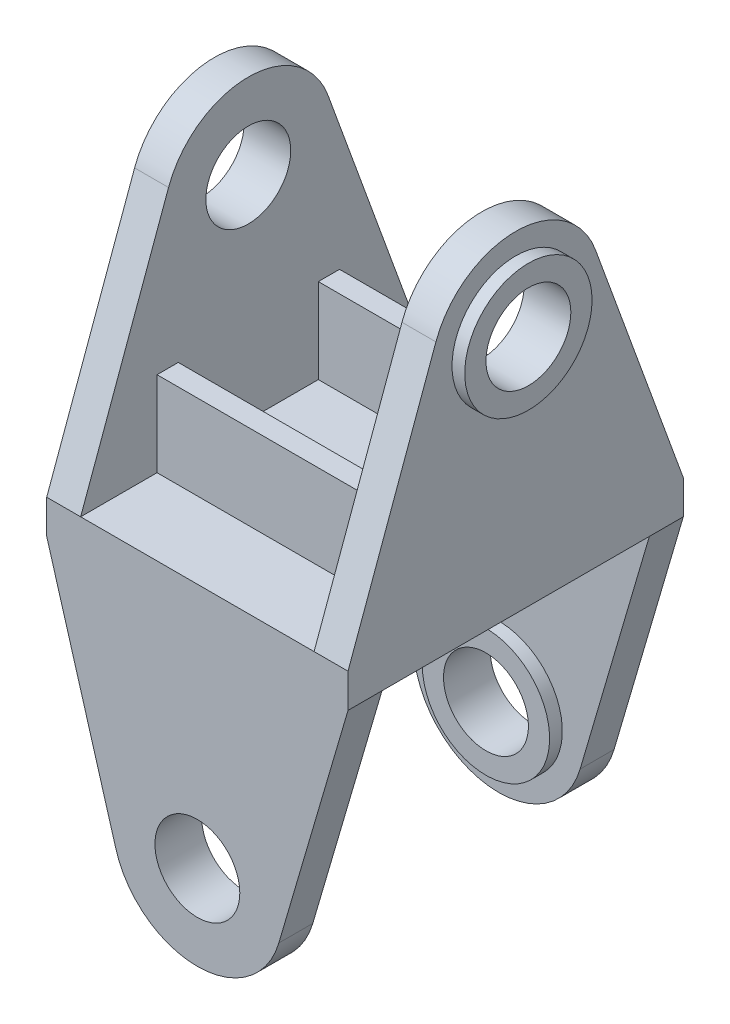
SolidWorks part; units mm, degrees
ref_plane "Front Plane" through (0, 0, 0) normal (0, 0, 1) x (1, 0, 0)
ref_plane "Top Plane" through (0, 0, 0) normal (0, 1, 0) x (1, 0, 0)
ref_plane "Right Plane" through (0, 0, 0) normal (1, 0, 0) x (0, 0, -1)
sketch "Sketch1" plane through (0, 0, 0) normal (1, 0, 0) x (0, 0, -1)
  line L0 (0, 0) -> (-17333.0338, 0) construction
  line L1 (0, 0) -> (0, -17333.0338) construction
  line L2 (39.5, -50) -> (18.7919, 6.8456)
  line L3 (-39.5, -50) -> (39.5, -50)
  line L4 (-39.5, -50) -> (-39.5, -58)
  line L5 (-39.5, -58) -> (39.5, -58)
  line L6 (39.5, -50) -> (39.5, -58)
  line L7 (0, -58) -> (0, -50) construction
  line L8 (-39.5, -54) -> (39.5, -54) construction
  line L9 (-39.5, -50) -> (-18.7919, 6.8456)
  circle A0 centre (0, 0) radius 10
  arc A1 (18.7919, 6.8456) -> (-18.7919, 6.8456) centre (0, 0) ccw
  circle A2 centre (0, 0) radius 15
  point P9 (0, -54)
  dimension "D1" = 20
  dimension "D2" = 30
  dimension "D3" = 40
  dimension "D4" = 79
  dimension "D5" = 8
  dimension "D6" = 50
extrude "Boss-Extrude1" add sketch "Sketch1" against normal blind 8 contours L2 A1 L9 L3 A2 | L6 L3 L4 L5 region at (0, -26.3684, 0) region at (0, -54, 0)
extrude "Boss-Extrude2" add sketch "Sketch1<3>" against normal blind 8 and the other way blind 3 contours A2 A0 region at (0, 0, 14.5757)
sketch "Sketch1<3>" plane through (0, 0, 0) normal (1, 0, 0) x (0, 0, -1) same geometry as "Sketch1"
extrude "Boss-Extrude3" add sketch "Sketch1<4>" against normal blind 8 from offset 63 separate body contours L2 A1 L9 L3 A2 | L6 L3 L4 L5 region at (0, -26.3684, 0) region at (0, -54, 0) offset against normal yes
sketch "Sketch1<4>" plane through (0, 0, 0) normal (1, 0, 0) x (0, 0, -1) same geometry as "Sketch1"
pattern_linear "LPattern3" count 2 spacing 66 along (-1, 0, 0) of "Boss-Extrude2"
sketch "Sketch3" plane through (0, 0, 39.5) normal (0, 0, 1) x (1, 0, 0)
  line L0 (0, -58) -> (-16.3077, -113.6265)
  line L1 (0, -58) -> (-71, -58)
  line L2 (0, -58) -> (0, -50)
  line L3 (0, -50) -> (-71, -50)
  line L4 (-71, -58) -> (-71, -50)
  line L5 (-71, -58) -> (-54.6923, -113.6265)
  arc A0 (-54.6923, -113.6265) -> (-16.3077, -113.6265) centre (-35.5, -108) ccw
  circle A1 centre (-35.5, -108) radius 15
  circle A2 centre (-35.5, -108) radius 10
  point P5 (0, 0)
  point P11 (-35.5, -58)
  line M8 (-63, -58) -> (-63, -50)
  line M9 (-63, -50) -> (-71, -50)
  line M10 (-71, -50) -> (-71, -58)
  line M11 (-71, -58) -> (-63, -58)
  dimension "D1" = 40
  dimension "D2" = 30
  dimension "D3" = 20
  dimension "D4" = 50
extrude "Boss-Extrude7" add sketch "Sketch3" against normal blind 8 contours L5 A0 L0 L1 A1 M11 | L2 L3 L1 M8 | M11 M8 M9 M10 region at (-35.5, -82.0322, 39.5) region at (-31.5, -54, 39.5) region at (-67, -54, 39.5)
extrude "Boss-Extrude8" add sketch "Sketch3<7>" against normal blind 11 contours A1 A2 region at (-50.0757, -108, 39.5)
sketch "Sketch3<7>" plane through (0, 0, 39.5) normal (0, 0, 1) x (1, 0, 0) same geometry as "Sketch3"
sketch "Sketch4" plane through (0, 0, -39.5) normal (0, 0, -1) x (-1, 0, 0)
  line L0 (71, -58) -> (54.6923, -113.6265) construction
  line L1 (71, -58) -> (0, -58)
  line L2 (71, -58) -> (71, -50)
  line L3 (71, -50) -> (0, -50)
  line L4 (0, -58) -> (0, -50)
  line L5 (0, -58) -> (16.3077, -113.6265) construction
  line L6 (71, -58) -> (54.6923, -113.6265)
  line L7 (0, -58) -> (16.3077, -113.6265)
  arc A0 (16.3077, -113.6265) -> (54.6923, -113.6265) centre (35.5, -108) ccw construction
  circle A1 centre (35.5, -108) radius 15 construction
  circle A2 centre (35.5, -108) radius 10 construction
  arc A3 (16.3077, -113.6265) -> (54.6923, -113.6265) centre (35.5, -108) ccw
  circle A4 centre (35.5, -108) radius 15
  circle A5 centre (35.5, -108) radius 10
  line M5 (0, -50) -> (0, -58)
  line M6 (0, -58) -> (8, -58)
  line M7 (8, -58) -> (8, -50)
  line M8 (8, -50) -> (0, -50)
extrude "Boss-Extrude9" add sketch "Sketch4" against normal blind 8 contours L7 A3 L6 L1 A4 M6 | L2 L3 L1 M7 | M8 M5 M6 M7 region at (-35.5, -82.0322, -39.5) region at (-39.5, -54, -39.5) region at (-4, -54, -39.5)
extrude "Boss-Extrude10" add sketch "Sketch4<4>" against normal blind 11 contours A4 A5 region at (-20.9243, -108, -39.5)
sketch "Sketch4<4>" plane through (0, 0, -39.5) normal (0, 0, -1) x (-1, 0, 0) same geometry as "Sketch4"
sketch "Sketch5" plane through (0, -50, 0) normal (0, 1, 0) x (1, 0, 0)
  line L1 (-63, 39.5) -> (-8, 39.5)
  line L2 (-63, 39.5) -> (-63, -39.5)
  line L3 (-63, -39.5) -> (-8, -39.5)
  line L4 (-8, 39.5) -> (-8, -39.5)
  line L5 (-63, -16.5) -> (-8, -16.5)
  line L6 (-63, -16.5) -> (-63, -21.5)
  line L7 (-63, -21.5) -> (-8, -21.5)
  line L8 (-8, -16.5) -> (-8, -21.5)
  line L9 (-63, 21.5) -> (-8, 21.5)
  line L10 (-63, 21.5) -> (-63, 16.5)
  line L11 (-63, 16.5) -> (-8, 16.5)
  line L12 (-8, 21.5) -> (-8, 16.5)
  line M9 (-63, -31.5) -> (-63, -39.5)
  line M10 (-63, -39.5) -> (-8, -39.5)
  line M11 (-8, -39.5) -> (-8, -31.5)
  line M12 (-8, -31.5) -> (-63, -31.5)
  dimension "D1" = 5
  dimension "D2" = 5
  dimension "D3" = 18
  dimension "D4" = 18
extrude "Boss-Extrude11" add sketch "Sketch5" against normal blind 8 contours M12 M9 M10 M11 | L7 L2 L4 M12 | L11 L2 L5 L4 | L2 L9 L4 L1 region at (-35.5, -50, -30.5) region at (-35.5, -50, 0) region at (-35.5, -50, 26.5) region at (-35.5, -50, 35.5)
extrude "Boss-Extrude13" add sketch "Sketch5<3>" along normal blind 20 and the other way blind 8 contours L2 L11 L4 L9 | L2 L7 L4 L5 region at (-35.5, -50, -19) region at (-35.5, -50, 19)
sketch "Sketch5<3>" plane through (0, -50, 0) normal (0, 1, 0) x (1, 0, 0) same geometry as "Sketch5"
